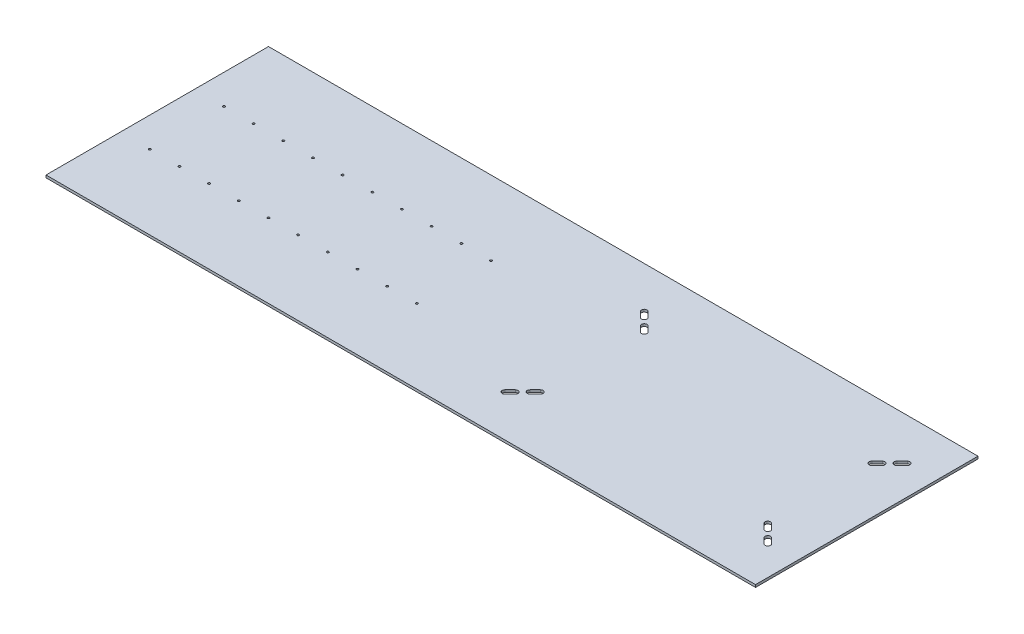
SolidWorks part; units mm, degrees
ref_plane "Front Plane" through (0, 0, 0) normal (0, 0, 1) x (1, 0, 0)
ref_plane "Top Plane" through (0, 0, 0) normal (0, 1, 0) x (1, 0, 0)
ref_plane "Right Plane" through (0, 0, 0) normal (1, 0, 0) x (0, 0, -1)
sketch "Sketch1" plane through (0, 0, 0) normal (0, 1, 0) x (1, 0, 0)
  line L1 (0, 0) -> (330.2, 0)
  line L2 (0, 0) -> (0, -228.6)
  line L3 (0, -228.6) -> (330.2, -228.6)
  line L4 (330.2, 0) -> (330.2, -228.6)
  dimension "D1" = 330.2
  dimension "D2" = 228.6
extrude "base plate" add sketch "Sketch1" against normal blind 2.54
sketch "center lines" plane through (0, 0, 0) normal (0, 1, 0) x (1, 0, 0)
  line L0 (165.1, 0) -> (165.1, -228.6) construction
  line L1 (330.2, 0) -> (0, 0) construction
  line L2 (0, -228.6) -> (330.2, -228.6) construction
  line L3 (0, -114.3) -> (330.2, -114.3) construction
  line L4 (0, 0) -> (0, -228.6) construction
  line L5 (330.2, -228.6) -> (330.2, 0) construction
sketch "Sketch3" plane through (0, 0, 0) normal (0, 1, 0) x (1, 0, 0)
  line L0 (21.0672, -185.8525) -> (30.0475, -194.8328)
  line L1 (30.0475, -194.8328) -> (60.5804, -164.2999)
  line L2 (60.5804, -164.2999) -> (51.6001, -155.3196)
  line L3 (51.6001, -155.3196) -> (21.0672, -185.8525)
  line L4 (29.9612, -185.9388) -> (35.3494, -180.5506) construction
  line L5 (28.0167, -183.9942) -> (33.4048, -178.6061)
  line L6 (31.9058, -187.8833) -> (37.2939, -182.4952)
  line L7 (0, -228.6) -> (330.2, -228.6) construction
  line L8 (48.2187, -167.6813) -> (42.8306, -173.0694) construction
  line L9 (50.1633, -169.6258) -> (44.7751, -175.014)
  line L10 (165.1, 0) -> (165.1, -228.6) construction
  line L11 (0, -114.3) -> (330.2, -114.3) construction
  line L12 (60.5804, -64.3001) -> (51.6001, -73.2804)
  line L13 (30.0475, -33.7672) -> (60.5804, -64.3001)
  line L14 (21.0672, -42.7475) -> (30.0475, -33.7672)
  line L15 (51.6001, -73.2804) -> (21.0672, -42.7475)
  line L16 (300.1525, -33.7672) -> (269.6196, -64.3001)
  line L17 (309.1328, -42.7475) -> (300.1525, -33.7672)
  line L18 (278.5999, -73.2804) -> (309.1328, -42.7475)
  line L19 (269.6196, -64.3001) -> (278.5999, -73.2804)
  line L20 (269.6196, -164.2999) -> (278.5999, -155.3196)
  line L21 (300.1525, -194.8328) -> (269.6196, -164.2999)
  line L22 (309.1328, -185.8525) -> (300.1525, -194.8328)
  line L23 (278.5999, -155.3196) -> (309.1328, -185.8525)
  line L24 (46.2742, -165.7367) -> (40.886, -171.1249)
  line L25 (29.9612, -42.6612) -> (35.3494, -48.0494) construction
  line L26 (28.0167, -44.6058) -> (33.4048, -49.9939)
  line L27 (31.9058, -40.7167) -> (37.2939, -46.1048)
  line L28 (48.2187, -60.9187) -> (42.8306, -55.5306) construction
  line L29 (50.1633, -58.9742) -> (44.7751, -53.586)
  line L30 (46.2742, -62.8633) -> (40.886, -57.4751)
  line L31 (300.2388, -42.6612) -> (294.8506, -48.0494) construction
  line L32 (302.1833, -44.6058) -> (296.7952, -49.9939)
  line L33 (298.2942, -40.7167) -> (292.9061, -46.1048)
  line L34 (281.9813, -60.9187) -> (287.3694, -55.5306) construction
  line L35 (280.0367, -58.9742) -> (285.4249, -53.586)
  line L36 (283.9258, -62.8633) -> (289.314, -57.4751)
  line L37 (281.9813, -167.6813) -> (287.3694, -173.0694) construction
  line L38 (280.0367, -169.6258) -> (285.4249, -175.014)
  line L39 (283.9258, -165.7367) -> (289.314, -171.1249)
  line L40 (300.2388, -185.9388) -> (294.8506, -180.5506) construction
  line L41 (302.1833, -183.9942) -> (296.7952, -178.6061)
  line L42 (298.2942, -187.8833) -> (292.9061, -182.4952)
  line L43 (51.6001, -164.2999) -> (51.6001, -155.3196)
  line L44 (60.5804, -164.2999) -> (51.6001, -164.2999)
  line L45 (51.6001, -64.3001) -> (51.6001, -73.2804)
  line L46 (60.5804, -64.3001) -> (51.6001, -64.3001)
  line L47 (278.5999, -64.3001) -> (278.5999, -73.2804)
  line L48 (269.6196, -64.3001) -> (278.5999, -64.3001)
  line L49 (278.5999, -164.2999) -> (278.5999, -155.3196)
  line L50 (269.6196, -164.2999) -> (278.5999, -164.2999)
  arc A0 (28.0167, -183.9942) -> (31.9058, -187.8833) centre (29.9612, -185.9388) ccw
  arc A1 (37.2939, -182.4952) -> (33.4048, -178.6061) centre (35.3494, -180.5506) ccw
  arc A2 (50.1633, -169.6258) -> (46.2742, -165.7367) centre (48.2187, -167.6813) ccw
  arc A3 (40.886, -171.1249) -> (44.7751, -175.014) centre (42.8306, -173.0694) ccw
  arc A4 (28.0167, -44.6058) -> (31.9058, -40.7167) centre (29.9612, -42.6612) cw
  arc A5 (37.2939, -46.1048) -> (33.4048, -49.9939) centre (35.3494, -48.0494) cw
  arc A6 (50.1633, -58.9742) -> (46.2742, -62.8633) centre (48.2187, -60.9187) cw
  arc A7 (40.886, -57.4751) -> (44.7751, -53.586) centre (42.8306, -55.5306) cw
  arc A8 (302.1833, -44.6058) -> (298.2942, -40.7167) centre (300.2388, -42.6612) ccw
  arc A9 (292.9061, -46.1048) -> (296.7952, -49.9939) centre (294.8506, -48.0494) ccw
  arc A10 (280.0367, -58.9742) -> (283.9258, -62.8633) centre (281.9813, -60.9187) ccw
  arc A11 (289.314, -57.4751) -> (285.4249, -53.586) centre (287.3694, -55.5306) ccw
  arc A12 (280.0367, -169.6258) -> (283.9258, -165.7367) centre (281.9813, -167.6813) cw
  arc A13 (289.314, -171.1249) -> (285.4249, -175.014) centre (287.3694, -173.0694) cw
  arc A14 (302.1833, -183.9942) -> (298.2942, -187.8833) centre (300.2388, -185.9388) cw
  arc A15 (292.9061, -182.4952) -> (296.7952, -178.6061) centre (294.8506, -180.5506) cw
  point P29 (32.6553, -183.2447)
  point P36 (45.5246, -170.3754)
  point P44 (32.6553, -45.3553)
  point P51 (45.5246, -58.2246)
  point P58 (297.5447, -45.3553)
  point P65 (284.6754, -58.2246)
  point P72 (284.6754, -170.3754)
  point P79 (297.5447, -183.2447)
  point P84 (37.2939, -178.6061)
  point P85 (40.886, -175.014)
  dimension "D6" = 2.75
  dimension "D10" = 5.08
  dimension "D9" = 2.032
  dimension "D1" = 43.18
  dimension "D2" = 12.7
  dimension "D3" = 45
  dimension "D4" = 99.9998
  dimension "D5" = 226.9998
  dimension "D7" = 7.62
  dimension "D8" = 6.35
extrude "Cut-Extrude9" cut sketch "Sketch3" against normal through all contours A5 L27 A4 L26 | L33 A9 L32 A8 | L36 A11 L35 A10 | A13 L39 A12 L38 | A15 L42 A14 L41 | L6 A1 L5 A0 | L24 A3 L9 A2 | L30 A7 L29 A6 region at (32.6553, 0, 45.3553) region at (297.5447, 0, 45.3553) region at (284.6754, 0, 58.2246) region at (284.6754, 0, 170.3754) region at (297.5447, 0, 183.2447)
sketch "Sketch4" plane through (0, 0, 0) normal (0, 1, 0) x (1, 0, 0)
  line L0 (0, -228.6) -> (330.2, -228.6) construction
  line L1 (0, 0) -> (-398.78, 0)
  line L2 (0, 0) -> (0, -228.6)
  line L3 (0, -228.6) -> (-398.78, -228.6)
  line L4 (-398.78, 0) -> (-398.78, -228.6)
  dimension "D1" = 398.78
extrude "Boss-Extrude1" add sketch "Sketch4" against normal up to surface (2.54 mm away) up to face at (297.5447, -2.54, 183.2447)
sketch "Sketch5" plane through (0, 0, 0) normal (0, 1, 0) x (1, 0, 0)
  line L0 (-398.78, -114.3) -> (330.2, -114.3) construction
  line L1 (-398.78, 0) -> (-398.78, -228.6) construction
  line L2 (330.2, -228.6) -> (330.2, 0) construction
  point P6 (-93.98, -152.4)
  point P7 (-93.98, -76.2)
  point P8 (-124.46, -152.4)
  point P10 (-124.46, -76.2)
  point P11 (-154.94, -152.4)
  point P12 (-154.94, -76.2)
  point P13 (-185.42, -152.4)
  point P14 (-185.42, -76.2)
  point P15 (-215.9, -152.4)
  point P16 (-215.9, -76.2)
  point P17 (-246.38, -152.4)
  point P18 (-246.38, -76.2)
  point P19 (-276.86, -152.4)
  point P20 (-276.86, -76.2)
  point P21 (-307.34, -152.4)
  point P22 (-307.34, -76.2)
  point P23 (-337.82, -152.4)
  point P24 (-337.82, -76.2)
  point P25 (-368.3, -152.4)
  point P26 (-368.3, -76.2)
  dimension "D1" = 304.8
  dimension "D2" = 38.1
  dimension "D4" = 30.48
  dimension "D3" = 10
hole_wizard "M2 Clearance Hole1" positions "Sketch6" profile "Sketch7" hole size "M2" standard "ISO" end condition through all
sketch "Sketch6" plane through (0, 0, 0) normal (0, 1, 0) x (1, 0, 0)
  point P0 (-93.98, -152.4)
  point P3 (-124.46, -152.4)
  point P6 (-154.94, -152.4)
  point P9 (-185.42, -152.4)
  point P12 (-215.9, -152.4)
  point P15 (-246.38, -152.4)
  point P18 (-276.86, -152.4)
  point P21 (-307.34, -152.4)
  point P24 (-337.82, -152.4)
  point P27 (-368.3, -152.4)
  point P30 (-368.3, -76.2)
  point P33 (-337.82, -76.2)
  point P36 (-307.34, -76.2)
  point P39 (-276.86, -76.2)
  point P42 (-246.38, -76.2)
  point P45 (-215.9, -76.2)
  point P48 (-185.42, -76.2)
  point P51 (-154.94, -76.2)
  point P54 (-124.46, -76.2)
  point P57 (-93.98, -76.2)
sketch "Sketch7" plane through (-93.98, 0, 152.4) normal (1, 0, 0) x (0, 0, 1)
  line L0 (0, 0) -> (0, 2.54)
  line L1 (0, 2.54) -> (1.1, 2.54)
  line L2 (1.1, 2.54) -> (1.1, 0)
  line L5 (1.1, 0) -> (0, 0)
  line L11 (0, -6.35) -> (0, 107.95) construction
  dimension "Thru Hole Dia." = 2.2
  dimension "Thru Hole Depth" = 2.54
